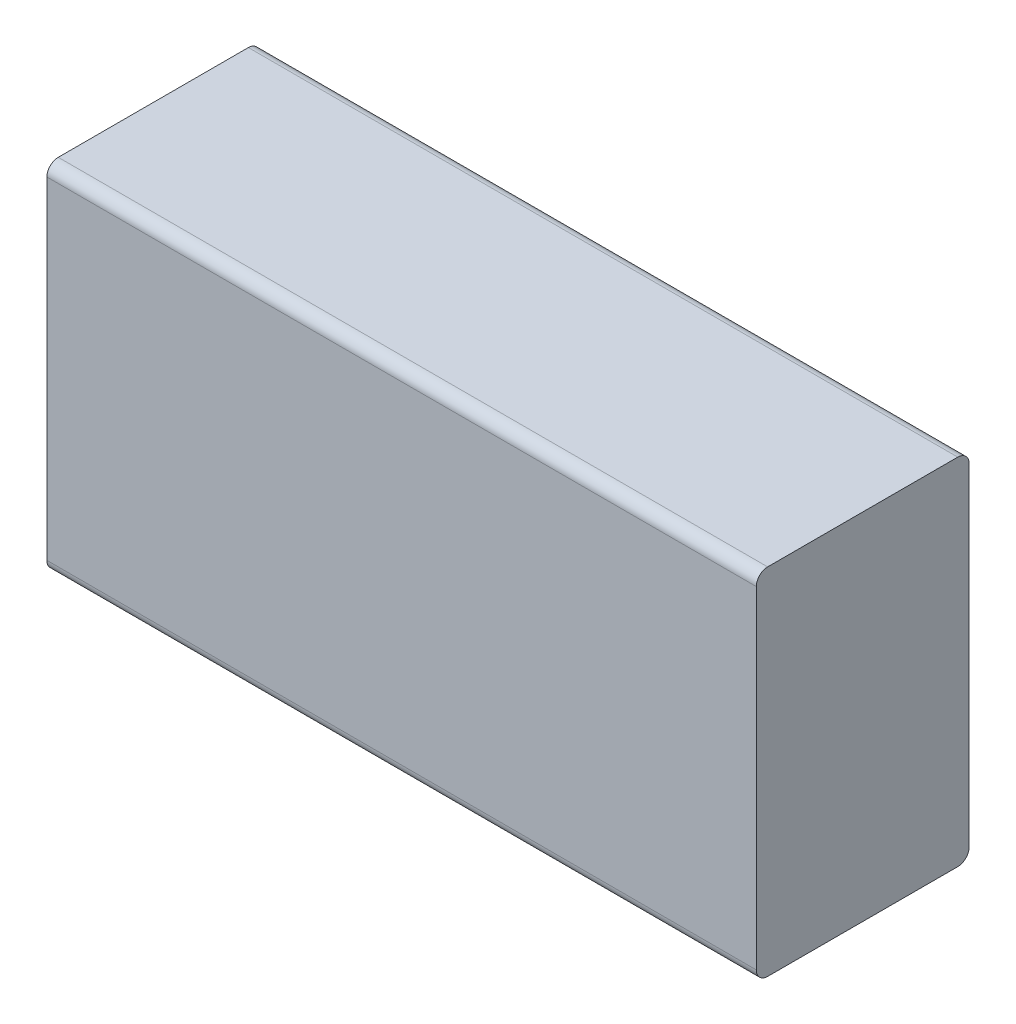
SolidWorks part; units mm, degrees
ref_plane "Front" through (0, 0, 0) normal (0, 0, 1) x (1, 0, 0)
ref_plane "Top" through (0, 0, 0) normal (0, 1, 0) x (1, 0, 0)
ref_plane "Right" through (0, 0, 0) normal (1, 0, 0) x (0, 0, -1)
sketch "Sketch1" plane through (0, 0, 0) normal (0, 0, 1) x (1, 0, 0)
  line L0 (0, 2.5) -> (-7.5, 2.5)
  line L1 (-7.5, -2.5) -> (0, -2.5)
  line L2 (-7.5, 2.5) -> (-7.5, -2.5)
  arc A2 (0, 2.5) -> (0, -2.5) centre (0, 0) cw
  dimension "b" = 5
  dimension "l" = 10
extrude "Extrude1" add sketch "Sketch1" along normal blind 3
sketch "Sketch2" plane through (0, 0, 0) normal (0, 0, 1) x (1, 0, 0)
  line L2 (2.5, 2.5) -> (2.5, -2.5)
  line L6 (0, 2.5) -> (-7.5, 2.5)
  line L7 (-7.5, 2.5) -> (-7.5, -2.5)
  line L8 (-7.5, -2.5) -> (0, -2.5)
  line L9 (2.5, 2.5) -> (-7.5, 2.5)
  line L10 (-7.5, 2.5) -> (-7.5, -2.5)
  line L11 (-7.5, -2.5) -> (2.5, -2.5)
  arc A3 (0, -2.5) -> (0, 2.5) centre (0, 0) ccw
  arc A4 (0, -2.5) -> (0, 2.5) centre (0, 0) ccw construction
  dimension "D1" = 0
extrude "Extrude2" add sketch "Sketch2" along normal blind 3
fillet "Fillet1" radius 0.16 4 edges at (-2.5, -2.5, 0) (-2.5, -2.5, 3) (-2.5, 2.5, 0) (-2.5, 2.5, 3)
equation "\"D1@Extrude2\" = \"h@Extrude1\""
